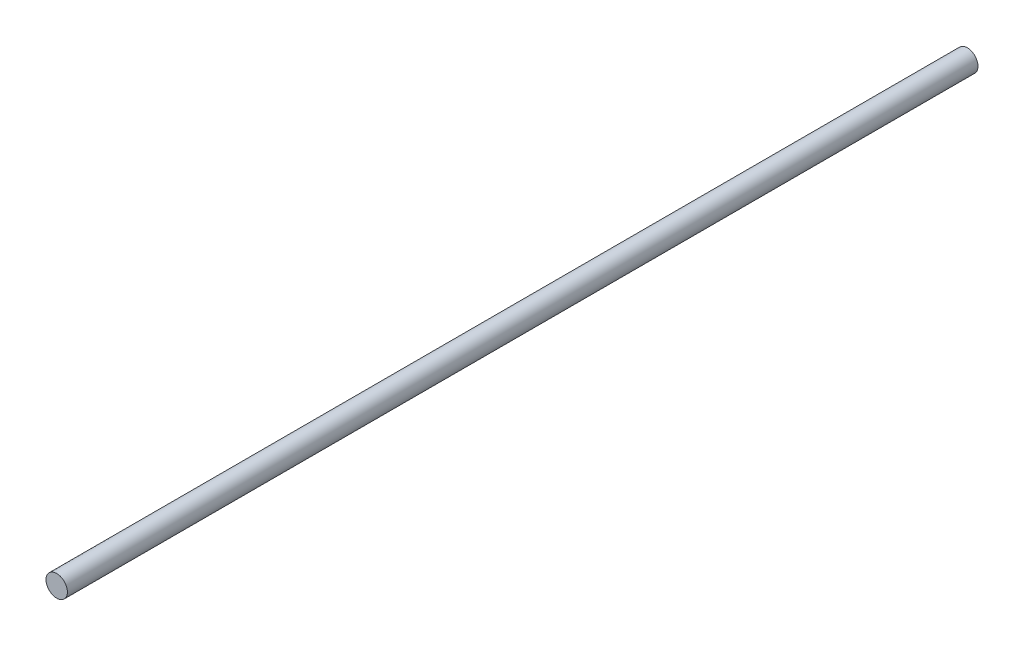
SolidWorks part; units mm, degrees
material "AISI 304"
ref_plane "Plano frontal" through (0, 0, 0) normal (0, 0, 1) x (1, 0, 0)
ref_plane "Plano superior" through (0, 0, 0) normal (0, 1, 0) x (1, 0, 0)
ref_plane "Plano direito" through (0, 0, 0) normal (1, 0, 0) x (0, 0, -1)
sketch "Esboço1" plane through (0, 0, 0) normal (0, 0, 1) x (1, 0, 0)
  circle A0 centre (0, 0) radius 4
  dimension "D1" = 8
extrude "Ressalto-extrusão1" add sketch "Esboço1" along normal blind 340
